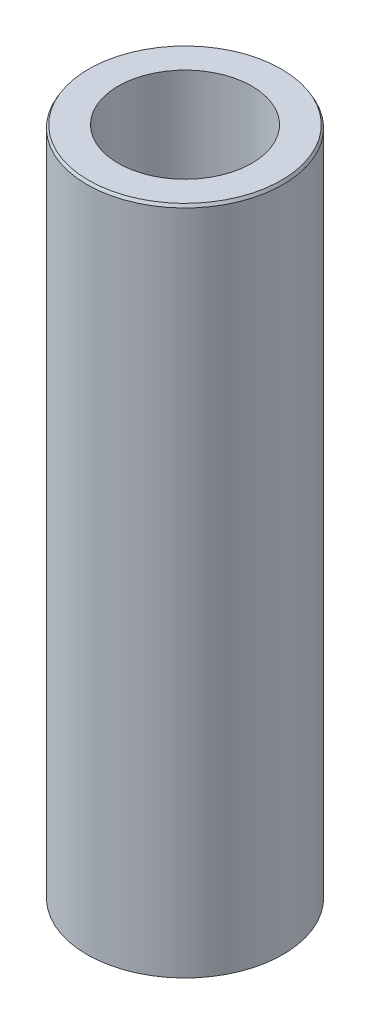
SolidWorks part; units mm, degrees
ref_plane "Front Plane" through (0, 0, 0) normal (0, 0, 1) x (1, 0, 0)
ref_plane "Top Plane" through (0, 0, 0) normal (0, 1, 0) x (1, 0, 0)
ref_plane "Right Plane" through (0, 0, 0) normal (1, 0, 0) x (0, 0, -1)
sketch "Sketch1" plane through (0, 0, 0) normal (0, 1, 0) x (1, 0, 0)
  circle A0 centre (0, 0) radius 35
  dimension "SHAFT_OD" = 70
extrude "Boss-Extrude1" add sketch "Sketch1" along normal blind 239.6823
sketch "Sketch2" plane through (0, 0, 0) normal (0, 1, 0) x (1, 0, 0)
  circle A0 centre (0, 0) radius 23.8771
  dimension "BORE_D" = 47.7542
extrude "Cut-Extrude1" cut sketch "Sketch2" along normal through all
chamfer "Chamfer1" distance 1.0145 angle 30 2 edges at (0, 239.6823, 35) (0, 0, 35) first distance on face at (0, 239.6823, 35) first distance on face at (0, 0, 23.8771)
